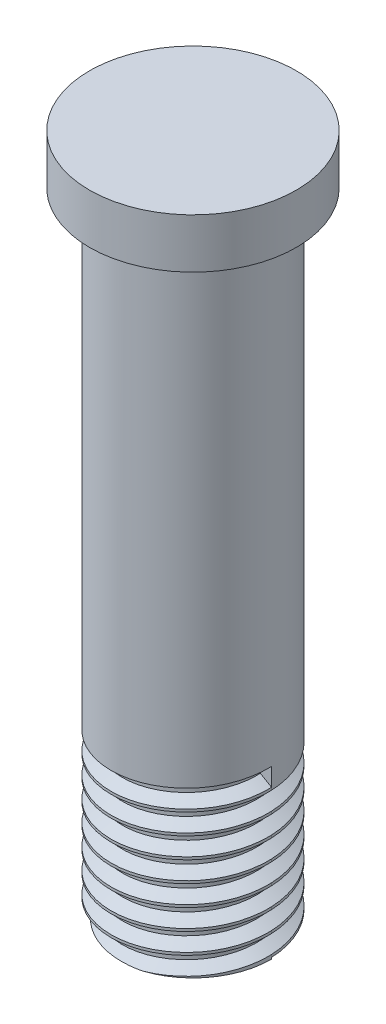
SolidWorks part; units mm, degrees
ref_plane "Front Plane" through (0, 0, 0) normal (0, 0, 1) x (1, 0, 0)
ref_plane "Top Plane" through (0, 0, 0) normal (0, 1, 0) x (1, 0, 0)
ref_plane "Right Plane" through (0, 0, 0) normal (1, 0, 0) x (0, 0, -1)
sketch "Sketch1" plane through (0, 0, 0) normal (0, 1, 0) x (1, 0, 0)
  circle A0 centre (0, 0) radius 4.75
  dimension "D1" = 9.5
extrude "Boss-Extrude1" add sketch "Sketch1" along normal blind 38
sketch "Sketch2" plane through (0, 38, 0) normal (0, 1, 0) x (1, 0, 0)
  circle A0 centre (0, 0) radius 6.25
  circle A1 centre (0, 0) radius 4.75 construction
  dimension "D1" = 1.5
extrude "Boss-Extrude2" add sketch "Sketch2" along normal blind 3
thread "Thread1" pitch 1.25 method cut profile "Thread Profile1" start angle 0, offset 1, length 10, pitch 1.25, diameter 9.5
ref_plane "Plane1" through (4.75, -1, 0) normal (0, 0, 1) x (1, 0, 0)
sketch "Thread Profile1" plane through (4.75, -1, 0) normal (0, 0, 1) x (1, 0, 0)
  line L0 (0, 0) -> (0, 1.25) construction
  line L11 (0, 0) -> (0, 1.0937)
  line L12 (0, 1.0937) -> (-0.6766, 0.7031)
  line L13 (-0.6766, 0.7031) -> (-0.6766, 0.3906)
  line L15 (-0.6766, 0.3906) -> (0, 0)
  line L17 (-0.6766, 0.5469) -> (0, 0.5469) construction
  point P2 (0, 0)
  dimension "Pitch" = 1.25
  dimension "Profile_Angle" = 60
  dimension "Profile_Land" = 0.3125
  dimension "Profile_Height" = 0.6766
